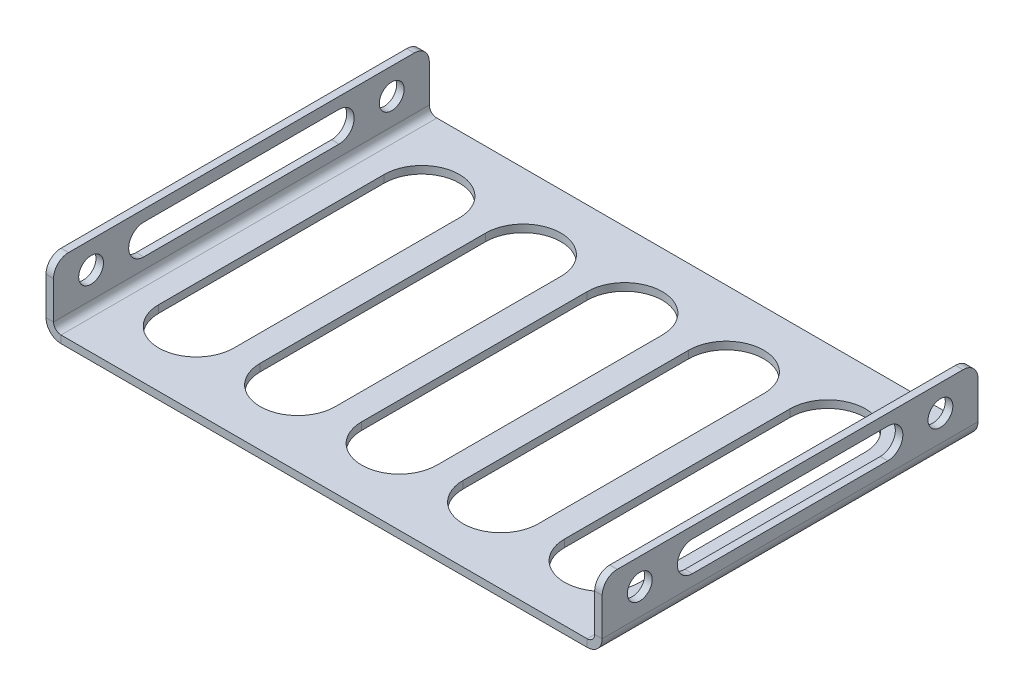
SolidWorks part; units mm, degrees
note: The reader was unsure of these and kept them because the rebuilt part matched: bend radius of "基体折弯1", "基体折弯2".
material "6061 合金"
ref_plane "前视基准面" through (0, 0, 0) normal (0, 0, 1) x (1, 0, 0)
ref_plane "上视基准面" through (0, 0, 0) normal (0, 1, 0) x (1, 0, 0)
ref_plane "右视基准面" through (0, 0, 0) normal (1, 0, 0) x (0, 0, -1)
sketch "草图1" plane through (0, 0, 0) normal (0, 0, 1) x (1, 0, 0)
  line L0 (-36, 8) -> (-36, 0)
  line L1 (-36, 0) -> (36, 0)
  line L2 (36, 0) -> (36, 8)
  dimension "D1" = 8
  dimension "D2" = 72
base flange "基体-法兰1" sketch "草图1" end condition mid plane depth 50 reverse direction no thickness 1 reverse thickness direction no bend radius 1
bend "基体折弯1" bend radius 1 bend angle 90 parameters "D5"=1
bend "基体折弯2" bend radius 1 bend angle 90 parameters "D5"=2
sketch "草图6" plane through (0, 0, 0) normal (1, 0, 0) x (0, 0, -1)
  line L0 (-13, 4.5) -> (13, 4.5) construction
  line L1 (0, 4.5) -> (0, 0) construction
  line L2 (-13, 6.5) -> (13, 6.5)
  line L3 (-13, 2.5) -> (13, 2.5)
  line L4 (-20, 4.5) -> (-15, 4.5) construction
  line L5 (15, 4.5) -> (20, 4.5) construction
  line L6 (-25, 8) -> (25, 8) construction
  circle A0 centre (-20, 4.5) radius 1.65
  circle A1 centre (20, 4.5) radius 1.65
  arc A2 (-13, 6.5) -> (-13, 2.5) centre (-13, 4.5) ccw
  arc A3 (13, 2.5) -> (13, 6.5) centre (13, 4.5) ccw
  point P9 (0, 4.5)
  dimension "D3" = 3.3
  dimension "D4" = 30
  dimension "D5" = 3.5
  dimension "D1" = 40
  dimension "D2" = 4
extrude "切除-拉伸1" cut sketch "草图6" against normal through all both and the other way through all
sketch "草图7" plane through (0, -1, 0) normal (0, -1, 0) x (1, 0, 0)
  line L0 (-27, 15) -> (-27, -15) construction
  line L1 (-22, 15) -> (-22, -15)
  line L2 (-32, 15) -> (-32, -15)
  line L3 (-35, 25) -> (35, 25) construction
  line L5 (-13.5, 15) -> (-13.5, -15) construction
  line L6 (-8.5, 15) -> (-8.5, -15)
  line L7 (-18.5, 15) -> (-18.5, -15)
  line L8 (0, 15) -> (0, -15) construction
  line L9 (5, 15) -> (5, -15)
  line L10 (-5, 15) -> (-5, -15)
  line L11 (13.5, 15) -> (13.5, -15) construction
  line L12 (18.5, 15) -> (18.5, -15)
  line L13 (8.5, 15) -> (8.5, -15)
  line L14 (27, 15) -> (27, -15) construction
  line L15 (32, 15) -> (32, -15)
  line L16 (22, 15) -> (22, -15)
  arc A0 (-22, 15) -> (-32, 15) centre (-27, 15) ccw
  arc A1 (-32, -15) -> (-22, -15) centre (-27, -15) ccw
  arc A2 (-8.5, 15) -> (-18.5, 15) centre (-13.5, 15) ccw
  arc A3 (-18.5, -15) -> (-8.5, -15) centre (-13.5, -15) ccw
  arc A4 (5, 15) -> (-5, 15) centre (0, 15) ccw
  arc A5 (-5, -15) -> (5, -15) centre (0, -15) ccw
  arc A6 (18.5, 15) -> (8.5, 15) centre (13.5, 15) ccw
  arc A7 (8.5, -15) -> (18.5, -15) centre (13.5, -15) ccw
  arc A8 (32, 15) -> (22, 15) centre (27, 15) ccw
  arc A9 (22, -15) -> (32, -15) centre (27, -15) ccw
  point P2 (-27, 0)
  point P7 (-27, 20)
  point P16 (-13.5, 0)
  point P22 (0, 0)
  point P29 (13.5, 0)
  point P36 (27, 0)
  dimension "D1" = 10
  dimension "D2" = 5
  dimension "D3" = 3.5
  dimension "D4" = 5
extrude "切除-拉伸2" cut sketch "草图7" against normal blind 10
fillet "圆角1" radius 2 4 edges at (36.5, 8, 25) (36.5, 8, -25) (-36.5, 8, -25) (-36.5, 8, 25)
sketch "折弯-线1" [suppressed] plane through (0, 0, 0) normal (0, 1, 0) x (1, 0, 0)
sketch "边界框1" [suppressed] plane through (0, 0, 0) normal (0, 1, 0) x (1, 0, 0)
sheet metal parameters "钣金6" thickness 1 parameters "D1"=1
flat pattern "平板型式6" [suppressed]
sketch "折弯-线2" plane through (0, 0, 0) normal (0, 1, 0) x (1, 0, 0)
sketch "边界框2" [suppressed] plane through (0, 0, 0) normal (0, 1, 0) x (1, 0, 0)
bend of the flat pattern "展平-<基体折弯1>1"
bend of the flat pattern "展平-<基体折弯2>1"
sheet metal parameters "钣金7" thickness 1 parameters "D1"=1
flat pattern "平板型式6" [suppressed]
sketch "折弯-线2" plane through (0, 0, 0) normal (0, 1, 0) x (1, 0, 0)
sketch "边界框2" [suppressed] plane through (0, 0, 0) normal (0, 1, 0) x (1, 0, 0)
bend of the flat pattern "展平-<基体折弯1>1"
bend of the flat pattern "展平-<基体折弯2>1"
sheet metal parameters "钣金8" thickness 1 parameters "D1"=1
flat pattern "平板型式6"
sketch "折弯-线2" plane through (0, 0, 0) normal (0, 1, 0) x (1, 0, 0)
  line L0 (-36.1781, -25) -> (-36.1781, 25) construction
  line L1 (36.1781, 25) -> (36.1781, -25) construction
  line L2 (-36.1781, -25) -> (-36.1781, 25) construction
  line L3 (36.1781, 25) -> (36.1781, -25) construction
sketch3d "边界框2" [suppressed]
  line L0 (-8.3562, 0, 0) -> (80.3562, 0, 0) construction
  line L1 (-8.3562, 50, 0) -> (80.3562, 50, 0) construction
  line L2 (-8.3562, 0, 0) -> (-8.3562, 50, 0) construction
  line L3 (80.3562, 0, 0) -> (80.3562, 50, 0) construction
bend of the flat pattern "展平-<基体折弯1>1"
bend of the flat pattern "展平-<基体折弯2>1"
